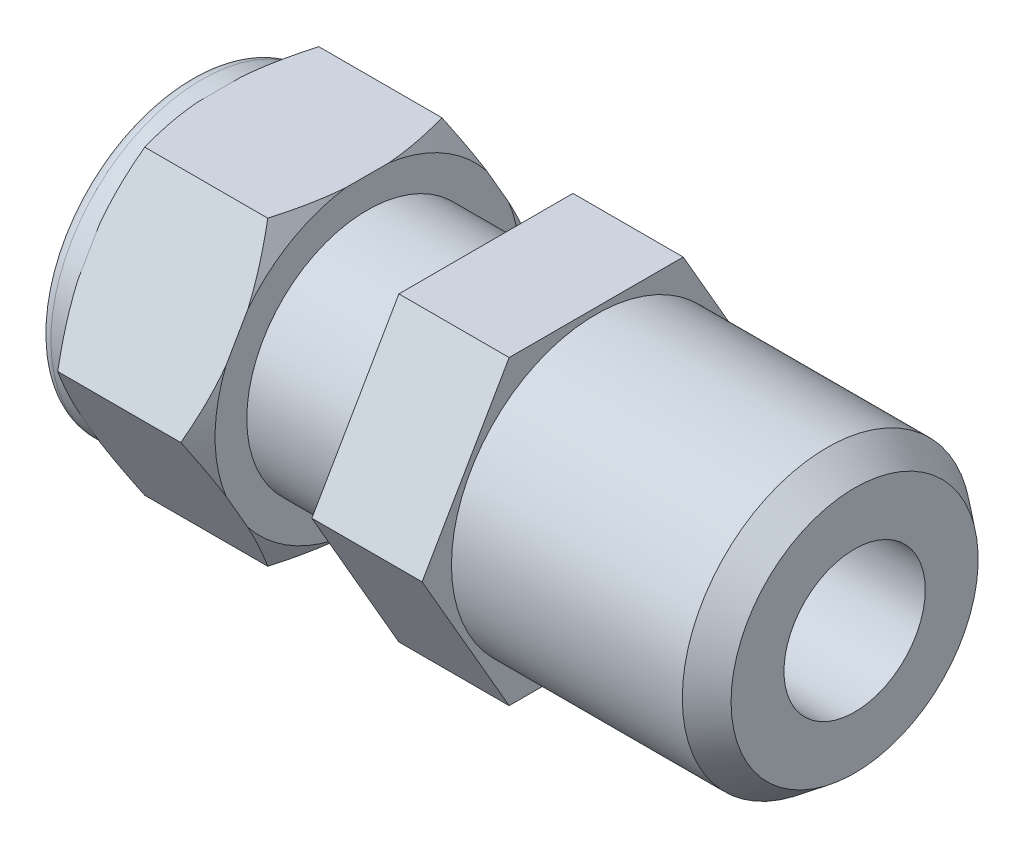
SolidWorks part; units mm, degrees
ref_plane "Front" through (0, 0, 0) normal (0, 0, 1) x (1, 0, 0)
ref_plane "Top" through (0, 0, 0) normal (0, 1, 0) x (1, 0, 0)
ref_plane "Right" through (0, 0, 0) normal (1, 0, 0) x (0, 0, -1)
sketch "BodySch" plane through (0, 0, 0) normal (0, 0, 1) x (1, 0, 0)
  line L0 (-103.6847, 0) -> (134.0726, 0) construction
  line L1 (-49.022, 0) -> (-49.022, 11.1125)
  line L2 (-49.022, 11.1125) -> (-41.3766, 11.1125)
  line L3 (-41.3766, 11.1125) -> (-41.3766, 8.89)
  line L4 (-41.3766, 8.89) -> (-27.178, 8.89)
  line L5 (-27.178, 8.89) -> (-27.178, 10.668)
  line L6 (-27.178, 10.668) -> (-2.0334, 10.668)
  line L7 (0, 9.1077) -> (-2.0334, 10.668)
  line L8 (-49.022, 0) -> (0, 0)
  line L9 (0, 9.1077) -> (0, 0)
  line L10 (-19.05, 10.668) -> (-19.05, 0) construction
  dimension "D1" = 37.5
  dimension "L4" = 19.05
revolve "Body" add sketch "BodySch" angle 360 about L0
sketch "Hex1Sch_G" plane through (-41.3766, 0, 0) normal (1, 0, 0) x (0, 0, -1)
  line L1 (12.8316, 0) -> (6.4158, 11.1125)
  line L2 (6.4158, 11.1125) -> (-6.4158, 11.1125)
  line L3 (-6.4158, 11.1125) -> (-12.8316, 0)
  line L4 (-12.8316, 0) -> (-6.4158, -11.1125)
  line L5 (-6.4158, -11.1125) -> (6.4158, -11.1125)
  line L6 (6.4158, -11.1125) -> (12.8316, 0)
  circle A0 centre (0, 0) radius 11.1125 construction
  dimension "G" = 22.225
extrude "Hex1" add sketch "Hex1Sch_G" along normal mid plane 10.922
sketch "PlaneCSch" plane through (0, 0, 0) normal (0, 0, 1) x (1, 0, 0)
  line L0 (-27.178, 10.668) -> (-27.178, -10.668) construction
  point P0 (-27.178, 5.1403)
fillet "BodyFillet" radius 0.889 1 edges at (-49.022, 0, 11.1125)
ref_plane "PlaneC" through (-27.178, 0, 0) normal (-1, 0, 0) x (0, 0, 1)
sketch "HexfilletSch" plane through (0, 0, 0) normal (0, 1, 0) x (1, 0, 0)
  line L0 (-46.8376, 11.2277) -> (-45.9116, 12.8316)
  line L1 (-46.8376, 12.8316) -> (-46.8376, 9.6237) construction
  line L2 (-35.9156, 12.8316) -> (-46.8376, 12.8316) construction
  line L3 (-35.9156, 12.8316) -> (-35.9156, 6.4158) construction
  line L5 (-35.9156, 11.2277) -> (-36.8416, 12.8316)
  line L6 (-46.8376, 11.2277) -> (-46.8376, 12.8316)
  line L7 (-35.9156, 11.2277) -> (-35.9156, 12.8316)
  line L8 (-46.8376, 12.8316) -> (-45.9116, 12.8316)
  line L9 (-41.9948, 0) -> (5.5242, 0) construction
  line L10 (-103.6847, 0) -> (134.0726, 0) construction
  line L12 (-35.9156, 12.8316) -> (-36.8416, 12.8316)
  dimension "D1" = 60
  dimension "D2" = 30
revolve "Hexfillet" cut sketch "HexfilletSch" angle 360 about L9
sketch "Hex2Sch_F" plane through (-27.178, 0, 0) normal (-1, 0, 0) x (0, 0, 1)
  line L3 (12.8316, 0) -> (6.4158, 11.1125)
  line L5 (6.4158, 11.1125) -> (-6.4158, 11.1125)
  line L7 (-6.4158, 11.1125) -> (-12.8316, 0)
  line L9 (-12.8316, 0) -> (-6.4158, -11.1125)
  line L11 (-6.4158, -11.1125) -> (6.4158, -11.1125)
  line L12 (6.4158, -11.1125) -> (12.8316, 0)
  circle A2 centre (0, 0) radius 11.1125 construction
  dimension "F" = 22.225
extrude "Hex2" add sketch "Hex2Sch_F" against normal blind 8.128
sketch "DSch" plane through (-49.022, 0, 0) normal (1, 0, 0) x (0, 0, -1)
  circle A0 centre (0, 0) radius 6.35
  dimension "T" = 12.7
extrude "Cut-ExtrudeD" cut sketch "DSch" along normal blind 22.86
sketch "E" plane through (0, 0, 0) normal (1, 0, 0) x (0, 0, -1)
  circle A0 centre (0, 0) radius 5.207
  dimension "E" = 10.414
extrude "Cut-ExtrudeE" cut sketch "E" against normal up to surface (26.162 mm away) up to face at (-26.162, 0, -6.35)
sketch "Sketch1" plane through (0, 0, 0) normal (0, 1, 0) x (1, 0, 0)
  line L0 (-19.05, -10.668) -> (-19.05, 10.668) construction
  line L1 (-26.162, 5.207) -> (-26.162, -5.207) construction
  point P0 (0, 0)
  point P1 (-26.162, 0)
  point P3 (-19.05, 0)
other "CPoint2" parameters "Diameter"=12.7, "StubLength"=0
ref_axis "Axis1" through (-36.162, 0, 0) along (1, 0, 0)
other "CPoint1" parameters "Diameter"=12.7, "StubLength"=0
ref_axis "Axis2" through (10, 0, 0) along (-1, 0, 0)
other "RPoint1"
equation "\"Hex1_middle_point@BodySch\"=\"C@BodySch\"*.35"
equation "\"Depth@Hex1\"=\"C@BodySch\"*.5"
equation "\"Depth@Hex2\"=\"Length@BodySch\"-\"L4@BodySch\"-\"C@BodySch\""
equation "\"Dia_ouside_D1@BodySch\"=\"G@Hex1Sch_G\""
equation "\"D1@BodyFillet\"=\"Dia_ouside_D1@BodySch\"/25"
